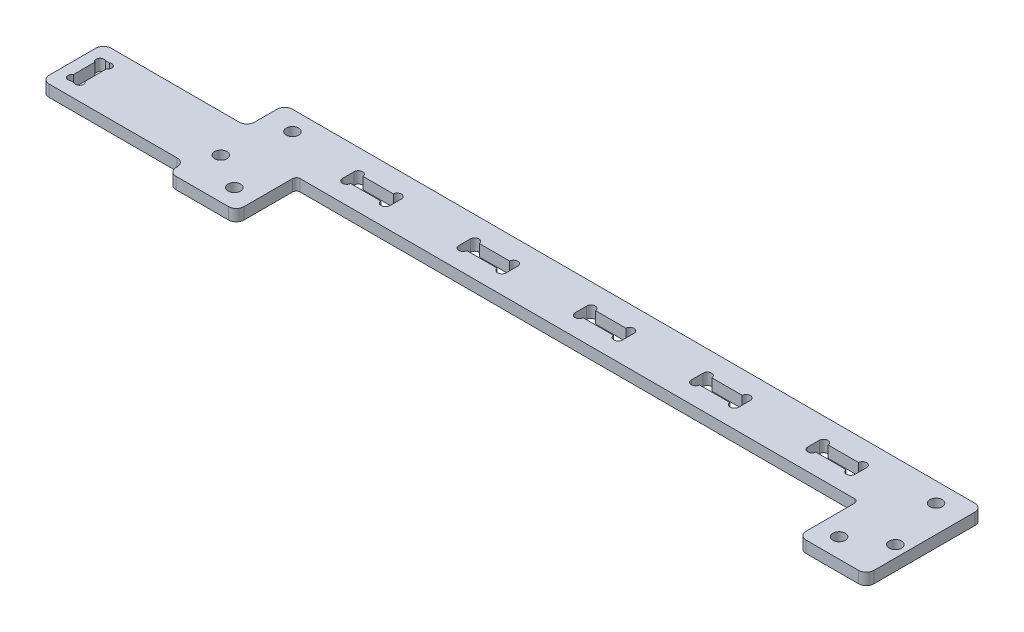
SolidWorks part; units mm, degrees
material "玻纤板"
ref_plane "前视基准面" through (0, 0, 0) normal (0, 0, 1) x (1, 0, 0)
ref_plane "上视基准面" through (0, 0, 0) normal (0, 1, 0) x (1, 0, 0)
ref_plane "右视基准面" through (0, 0, 0) normal (1, 0, 0) x (0, 0, -1)
sketch "草图1" plane through (0, 0, 0) normal (0, 1, 0) x (1, 0, 0)
  line L0 (78, -10) -> (78, -15) construction
  line L1 (-90, -15) -> (-72.5, -15)
  line L2 (-90, -15) -> (-90, 15)
  line L3 (-90, 15) -> (90, 15)
  line L4 (90, -15) -> (90, 15)
  line L5 (0, 15) -> (0, -7.25) construction
  line L6 (-90, 0) -> (90, 0) construction
  line L7 (-72.5, 0.5) -> (72.5, 0.5)
  line L8 (-72.5, 0.5) -> (-72.5, -15)
  line L10 (72.5, 0.5) -> (72.5, -15)
  line L11 (0, -7.25) -> (0, 0.5) construction
  line L12 (-72.5, -7.25) -> (72.5, -7.25) construction
  line L13 (72.5, -15) -> (90, -15)
  line L14 (-83, 10) -> (-78, -10) construction
  circle A0 centre (78, -10) radius 1.6
  circle A1 centre (-78, -10) radius 1.6
  circle A2 centre (-83, 10) radius 1.6
  circle A4 centre (83, 10) radius 1.6
  point P0 (0, 0)
  point P4 (0, -7.25)
  dimension "D3" = 3.2
  dimension "D7" = 10.5
  dimension "D8" = 3.2
  dimension "D1" = 156
  dimension "D2" = 145
  dimension "D4" = 180
  dimension "D5" = 30
  dimension "D6" = 5
  dimension "D9" = 25
  dimension "D10" = 5
extrude "凸台-拉伸1" add sketch "草图1" along normal blind 3
ref_axis "基准轴1" through (-78, 3, 10) along (0, -1, 0)
ref_axis "基准轴2" through (-83, 3, -10) along (0, -1, 0)
ref_plane "基准面1" through (-75.7647, 0, 18.9412) normal (-0.9701, 0, 0.2425) x (0.2425, 0, 0.9701)
sketch "草图3" plane through (0, 3, 0) normal (0, 1, 0) x (1, 0, 0)
  line L0 (0, 0.5) -> (0, 15) construction
  line L1 (-72.5, 0.5) -> (72.5, 0.5) construction
  line L2 (90, 15) -> (-90, 15) construction
  line L7 (-90, 15) -> (-90, -15) construction
  line L8 (-90, -15) -> (-72.5, -15) construction
  circle A13 centre (87, -4.5) radius 1.6
  circle A40 centre (-87, -4.5) radius 1.6
  dimension "D2" = 3.2
  dimension "D1" = 3
  dimension "D3" = 10.5
extrude "切除-拉伸1" cut sketch "草图3" against normal through all
sketch "草图4" plane through (0, 0, 0) normal (0, -1, 0) x (1, 0, 0)
  line L0 (0, 0) -> (0, -15) construction
  line L1 (66, -9) -> (54, -9)
  line L2 (66, -9) -> (66, -6)
  line L3 (66, -6) -> (54, -6)
  line L4 (54, -9) -> (54, -6)
  line L5 (60, -6) -> (60, -9) construction
  line L6 (66, -7.5) -> (54, -7.5) construction
  line L7 (90, -15) -> (-90, -15) construction
  line L8 (0, -7.5) -> (54, -7.5) construction
  line L9 (36, -9) -> (36, -6)
  line L10 (36, -9) -> (24, -9)
  line L11 (24, -9) -> (24, -6)
  line L12 (36, -6) -> (24, -6)
  line L13 (6, -9) -> (6, -6)
  line L14 (6, -9) -> (-6, -9)
  line L15 (-6, -9) -> (-6, -6)
  line L16 (6, -6) -> (-6, -6)
  line L17 (-24, -9) -> (-24, -6)
  line L18 (-24, -9) -> (-36, -9)
  line L19 (-36, -9) -> (-36, -6)
  line L20 (-24, -6) -> (-36, -6)
  line L21 (-54, -9) -> (-54, -6)
  line L22 (-54, -9) -> (-66, -9)
  line L23 (-66, -9) -> (-66, -6)
  line L24 (-54, -6) -> (-66, -6)
  point P56 (60, -7.5)
  dimension "D1" = 12
  dimension "D2" = 3
  dimension "D3" = 60
  dimension "D5" = 30
  dimension "D4" = 5
fillet "圆角1" radius 1 2 edges at (72.5, 1.5, -0.5) (-72.5, 1.5, -0.5)
extrude "切除-拉伸2" cut sketch "草图4" against normal through all
sketch "草图5" plane through (0, 0, 0) normal (0, -1, 0) x (1, 0, 0)
  line L0 (54, -9) -> (66, -9) construction
  line L1 (54, -7.5) -> (60, -7.5) construction
  line L2 (54, -6) -> (54, -9) construction
  line L3 (60, -7.5) -> (60, -6) construction
  line L4 (66, -6) -> (54, -6) construction
  line L5 (24, -7.5) -> (30, -7.5) construction
  line L6 (30, -7.5) -> (30, -6) construction
  line L7 (-6, -7.5) -> (0, -7.5) construction
  line L8 (0, -7.5) -> (0, -6) construction
  line L9 (-36, -7.5) -> (-30, -7.5) construction
  line L10 (-30, -7.5) -> (-30, -6) construction
  line L11 (-66, -7.5) -> (-60, -7.5) construction
  line L12 (-60, -7.5) -> (-60, -6) construction
  circle A0 centre (65, -9) radius 1
  circle A1 centre (55, -9) radius 1
  circle A2 centre (55, -6) radius 1
  circle A3 centre (65, -6) radius 1
  circle A4 centre (35, -9) radius 1
  circle A5 centre (25, -9) radius 1
  circle A6 centre (25, -6) radius 1
  circle A7 centre (35, -6) radius 1
  circle A8 centre (5, -9) radius 1
  circle A9 centre (-5, -9) radius 1
  circle A10 centre (-5, -6) radius 1
  circle A11 centre (5, -6) radius 1
  circle A12 centre (-25, -9) radius 1
  circle A13 centre (-35, -9) radius 1
  circle A14 centre (-35, -6) radius 1
  circle A15 centre (-25, -6) radius 1
  circle A16 centre (-55, -9) radius 1
  circle A17 centre (-65, -9) radius 1
  circle A18 centre (-65, -6) radius 1
  circle A19 centre (-55, -6) radius 1
  dimension "D1" = 2
  dimension "D3" = 20
  dimension "D2" = 5
extrude "切除-拉伸3" cut sketch "草图5" against normal through all
sketch "草图6" plane through (0, 0, 0) normal (0, -1, 0) x (1, 0, 0)
  line L4 (36.1, -9) -> (36.1, -6)
  line L5 (33.9046, -5.9) -> (26.0954, -5.9)
  line L6 (23.9, -6) -> (23.9, -9)
  line L7 (26.0954, -9.1) -> (33.9046, -9.1)
  line L8 (66.1, -9) -> (66.1, -6)
  line L9 (63.9046, -5.9) -> (56.0954, -5.9)
  line L10 (53.9, -6) -> (53.9, -9)
  line L11 (56.0954, -9.1) -> (63.9046, -9.1)
  line L12 (66.1, -9) -> (66.1, -6)
  line L13 (63.9046, -5.9) -> (56.0954, -5.9)
  line L14 (53.9, -6) -> (53.9, -9)
  line L15 (56.0954, -9.1) -> (63.9046, -9.1)
  line L16 (6.1, -9) -> (6.1, -6)
  line L17 (3.9046, -5.9) -> (-3.9046, -5.9)
  line L18 (-6.1, -6) -> (-6.1, -9)
  line L19 (-3.9046, -9.1) -> (3.9046, -9.1)
  line L20 (-23.9, -9) -> (-23.9, -6)
  line L21 (-26.0954, -5.9) -> (-33.9046, -5.9)
  line L22 (-36.1, -6) -> (-36.1, -9)
  line L23 (-33.9046, -9.1) -> (-26.0954, -9.1)
  line L24 (-53.9, -9) -> (-53.9, -6)
  line L25 (-56.0954, -5.9) -> (-63.9046, -5.9)
  line L26 (-66.1, -6) -> (-66.1, -9)
  line L27 (-63.9046, -9.1) -> (-56.0954, -9.1)
  arc A4 (33.9046, -9.1) -> (36.1, -9) centre (35, -9) ccw
  arc A5 (36.1, -6) -> (33.9046, -5.9) centre (35, -6) ccw
  arc A6 (26.0954, -5.9) -> (23.9, -6) centre (25, -6) ccw
  arc A7 (23.9, -9) -> (26.0954, -9.1) centre (25, -9) ccw
  arc A8 (63.9046, -9.1) -> (66.1, -9) centre (65, -9) ccw
  arc A9 (66.1, -6) -> (63.9046, -5.9) centre (65, -6) ccw
  arc A10 (56.0954, -5.9) -> (53.9, -6) centre (55, -6) ccw
  arc A11 (53.9, -9) -> (56.0954, -9.1) centre (55, -9) ccw
  arc A12 (63.9046, -9.1) -> (66.1, -9) centre (65, -9) ccw
  arc A13 (66.1, -6) -> (63.9046, -5.9) centre (65, -6) ccw
  arc A14 (56.0954, -5.9) -> (53.9, -6) centre (55, -6) ccw
  arc A15 (53.9, -9) -> (56.0954, -9.1) centre (55, -9) ccw
  arc A16 (3.9046, -9.1) -> (6.1, -9) centre (5, -9) ccw
  arc A17 (6.1, -6) -> (3.9046, -5.9) centre (5, -6) ccw
  arc A18 (-3.9046, -5.9) -> (-6.1, -6) centre (-5, -6) ccw
  arc A19 (-6.1, -9) -> (-3.9046, -9.1) centre (-5, -9) ccw
  arc A20 (-26.0954, -9.1) -> (-23.9, -9) centre (-25, -9) ccw
  arc A21 (-23.9, -6) -> (-26.0954, -5.9) centre (-25, -6) ccw
  arc A22 (-33.9046, -5.9) -> (-36.1, -6) centre (-35, -6) ccw
  arc A23 (-36.1, -9) -> (-33.9046, -9.1) centre (-35, -9) ccw
  arc A24 (-56.0954, -9.1) -> (-53.9, -9) centre (-55, -9) ccw
  arc A25 (-53.9, -6) -> (-56.0954, -5.9) centre (-55, -6) ccw
  arc A26 (-63.9046, -5.9) -> (-66.1, -6) centre (-65, -6) ccw
  arc A27 (-66.1, -9) -> (-63.9046, -9.1) centre (-65, -9) ccw
  dimension "D3" = 30
  dimension "D1" = 0.1
  dimension "D2" = 5
extrude "切除-拉伸4" cut sketch "草图6" against normal through all
sketch "草图7" plane through (0, 0, 0) normal (0, -1, 0) x (1, 0, 0)
  line L0 (-90, -15) -> (-90, 15) construction
  line L6 (-124, 7.25) -> (-121, 7.25)
  line L7 (-71.5, -0.5) -> (71.5, -0.5) construction
  line L31 (-124, 7.25) -> (-124, -1.75)
  line L32 (-90, 2.75) -> (-127, 2.75) construction
  line L48 (-124, -1.75) -> (-121, -1.75)
  line L49 (-90, -5.25) -> (-127, -5.25)
  line L50 (-127, -5.25) -> (-127, 10.75)
  line L51 (-127, 10.75) -> (-90, 10.75)
  line L52 (-90, 10.75) -> (-90, -5.25)
  line L53 (-121, 7.25) -> (-121, -1.75)
  line L54 (-122.5, -1.75) -> (-122.5, 7.25) construction
  line L55 (-90, -15) -> (-90, 15) construction
  line L56 (-124, 2.75) -> (-121, 2.75) construction
  point P10 (-122.5, 2.75)
  dimension "D2" = 3
  dimension "D1" = 3.25
  dimension "D3" = 8
  dimension "D6" = 9
  dimension "D8" = 37
  dimension "D9" = 3
extrude "凸台-拉伸2" add sketch "草图7" against normal up to surface (3 mm away) up to face at (-60, 3, -7.5)
sketch "草图8" plane through (0, 3, 0) normal (0, 1, 0) x (1, 0, 0)
  line L1 (-124, -2.75) -> (-121, -2.75) construction
  line L2 (-124, 1.75) -> (-124, -7.25) construction
  line L3 (-123.005, 1.75) -> (-121.995, 1.75) construction
  line L4 (-122.5, -2.75) -> (-122.5, -7.25) construction
  line L5 (-124, -7.25) -> (-121, -7.25) construction
  line L6 (-121, -7.25) -> (-121, 1.75) construction
  line L7 (-121, 1.75) -> (-124, 1.75) construction
  circle A14 centre (-123.5025, 0.8825) radius 1
  circle A15 centre (-121.4975, 0.8825) radius 1
  circle A16 centre (-121.4975, -6.3825) radius 1
  circle A17 centre (-123.5025, -6.3825) radius 1
  dimension "D1" = 1.01
  dimension "D2" = 2
extrude "切除-拉伸5" cut sketch "草图8" against normal through all
fillet "圆角3" radius 2 10 edges at (90, 1.5, 15) (72.5, 1.5, 15) (-72.5, 1.5, 15) (-90, 1.5, 15) (90, 1.5, -15) (-127, 1.5, -5.25) (-90, 1.5, -5.25) (-90, 1.5, -15) (-127, 1.5, 10.75) (-90, 1.5, 10.75)
